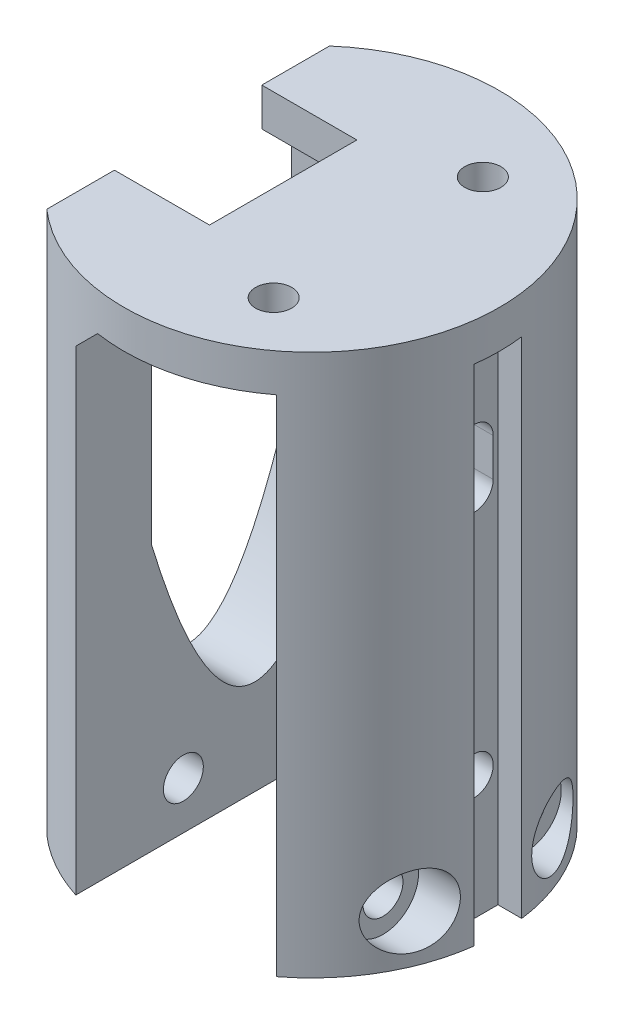
SolidWorks part; units mm, degrees
ref_plane "Front Plane" through (0, 0, 0) normal (0, 0, 1) x (1, 0, 0)
ref_plane "Top Plane" through (0, 0, 0) normal (0, 1, 0) x (1, 0, 0)
ref_plane "Right Plane" through (0, 0, 0) normal (1, 0, 0) x (0, 0, -1)
sketch "Sketch2" plane through (0, 0, 0) normal (0, 1, 0) x (1, 0, 0)
  line L0 (-3.81, 24.7914) -> (-3.81, -24.7914) construction
  line L1 (-16.51, -18.8826) -> (-16.51, -9.8425)
  line L2 (-20.2803, -9.8425) -> (16.2877, -9.8425) construction
  line L3 (-16.51, -9.8425) -> (-3.81, -9.8425)
  line L4 (-3.81, -9.8425) -> (-3.81, 9.8425)
  line L5 (16.2877, 9.8425) -> (-20.2803, 9.8425) construction
  line L6 (-3.81, 9.8425) -> (-16.51, 9.8425)
  line L7 (-16.51, 9.8425) -> (-16.51, 18.8826)
  line L8 (-16.51, -18.8826) -> (-16.51, 18.8826) construction
  circle A2 centre (0, 0) radius 25.0825 construction
  arc A3 (-16.51, -18.8826) -> (-16.51, 18.8826) centre (0, 0) ccw
  dimension "D1" = 3.81
  dimension "D2" = 16.51
  dimension "D3" = 25.0825
extrude "plate" add sketch "Sketch2" along normal blind 5.08
sketch "Sketch15" plane through (0, 0, 0) normal (0, -1, 0) x (1, 0, 0)
  circle A1 centre (8.89, 13.97) radius 2.413
  circle A2 centre (8.89, 13.97) radius 2.413 construction
  circle A3 centre (8.89, -13.97) radius 2.413
  circle A4 centre (8.89, -13.97) radius 2.413 construction
extrude "boltholes" cut sketch "Sketch15" against normal up to next
sketch "Sketch16" plane through (0, 0, 0) normal (0, -1, 0) x (1, 0, 0)
  line L5 (24.8807, 3.175) -> (24.8807, -3.175) construction
  line L6 (15.24, 19.9217) -> (15.24, -19.9217)
  line L12 (0, 0) -> (24.8807, 0) construction
  line L13 (24.8807, 3.175) -> (21.7057, 3.175)
  line L14 (21.7057, 3.175) -> (21.7057, -3.175)
  line L15 (21.7057, -3.175) -> (24.8807, -3.175)
  arc A0 (-16.51, -18.8826) -> (-16.51, 18.8826) centre (0, 0) ccw construction
  arc A2 (15.24, 19.9217) -> (24.8807, 3.175) centre (0, 0) cw
  arc A3 (15.24, -19.9217) -> (24.8807, -3.175) centre (0, 0) ccw
  dimension "D1" = 6.35
  dimension "D4" = 15.24
  dimension "D2" = 3.175
extrude "upright" add sketch "Sketch16" along normal blind 67.31
sketch "Sketch19" plane through (0, 0, 0) normal (0, -1, 0) x (1, 0, 0)
  line L0 (-16.51, 13.8026) -> (-7.62, 13.8026)
  line L1 (-16.51, 9.8425) -> (-16.51, 18.8826) construction
  line L2 (-7.62, 13.8026) -> (-7.62, 23.897)
  line L3 (-16.51, 18.8826) -> (-16.51, 13.8026)
  line L4 (-3.81, 0) -> (15.24, 0) construction
  line L5 (-3.81, -9.8425) -> (-3.81, 9.8425) construction
  line L6 (15.24, 19.9217) -> (15.24, -19.9217) construction
  line L7 (-7.62, -13.8026) -> (-7.62, -23.897)
  line L8 (-16.51, -13.8026) -> (-7.62, -13.8026)
  line L9 (-16.51, -18.8826) -> (-16.51, -13.8026)
  line L10 (15.24, 19.9217) -> (15.24, -19.9217) construction
  arc A0 (15.24, 19.9217) -> (-16.51, 18.8826) centre (0, 0) ccw construction
  arc A1 (-16.51, 18.8826) -> (-7.62, 23.897) centre (0, 0) cw
  arc A2 (-16.51, -18.8826) -> (-7.62, -23.897) centre (0, 0) ccw
  dimension "D1" = 8.89
  dimension "D2" = 5.08
  dimension "D3" = 22.86
  dimension "D4" = 7.62
extrude "second_side_legs" add sketch "Sketch19" along normal blind 31.75
sketch "Sketch20" plane through (0, -31.75, 0) normal (0, -1, 0) x (1, 0, 0)
  line L0 (-16.51, 18.8826) -> (-16.51, -18.8826)
  line L1 (-7.62, 23.897) -> (-7.62, -23.897)
  arc A0 (-16.51, 18.8826) -> (-7.62, 23.897) centre (0, 0) cw
  arc A1 (-16.51, -18.8826) -> (-7.62, -23.897) centre (0, 0) ccw
extrude "second_side_face" add sketch "Sketch20" along normal up to surface (35.56 mm away) up to face at (21.168, -67.31, 0)
sketch "Sketch21" plane through (-16.51, 0, 0) normal (-1, 0, 0) x (0, 0, 1)
  line L0 (13.8026, -31.75) -> (-13.8026, -31.75) construction
  line L1 (-13.8026, -31.75) -> (-13.8026, 0) construction
  line L2 (0, -31.75) -> (0, -52.5265) construction
  line L3 (-13.8026, -31.75) -> (13.8026, -31.75)
  parabola Q0 (-13.8026, -31.75) -> (13.8026, -31.75) focus (0, -52.5265) apex (0, -54.61)
  dimension "D1" = 22.86
extrude "archway" cut sketch "Sketch21" against normal up to next
sketch "Sketch17" plane through (15.24, 0, 0) normal (-1, 0, 0) x (0, 0, 1)
  line L0 (0, 0) -> (0, -67.31) construction
  line L1 (-9.8425, 0) -> (9.8425, 0) construction
  line L2 (-3.175, -67.31) -> (3.175, -67.31) construction
  line L3 (0, -12.7) -> (0, -17.78) construction
  line L4 (2.54, -12.7) -> (2.54, -17.78)
  line L5 (-2.54, -12.7) -> (-2.54, -17.78)
  line L6 (-9.525, -60.96) -> (9.525, -60.96) construction
  arc A1 (2.54, -12.7) -> (-2.54, -12.7) centre (0, -12.7) ccw
  arc A2 (-2.54, -17.78) -> (2.54, -17.78) centre (0, -17.78) ccw
  circle A3 centre (0, -50.8) radius 2.54
  circle A6 centre (-9.525, -60.96) radius 2.667
  circle A7 centre (9.525, -60.96) radius 2.667
  point P8 (0, -15.24)
  point P17 (0, -60.96)
  dimension "D1" = 5.08
  dimension "D3" = 12.7
  dimension "D4" = 5.08
  dimension "D6" = 10.16
  dimension "D7" = 19.05
  dimension "D8" = 5.334
  dimension "D9" = 5.334
  dimension "D2" = 5.08
  dimension "D5" = 38.1
extrude "upright_holes" cut sketch "Sketch17" along normal through all both and the other way through all
sketch "Sketch22" plane through (15.24, 0, 0) normal (-1, 0, 0) x (0, 0, 1)
  circle A0 centre (-9.525, -60.96) radius 4.7625
  circle A1 centre (9.525, -60.96) radius 4.7625
  dimension "D1" = 9.525
extrude "lower_connecting_boltholes" cut sketch "Sketch22" against normal blind 6.35 from offset 3.81 offset against normal yes
chamfer "Chamfer1" distance 3.81 angle 45 2 edges at (-7.62, 0, -18.8498) (-7.62, 0, 18.8498)
